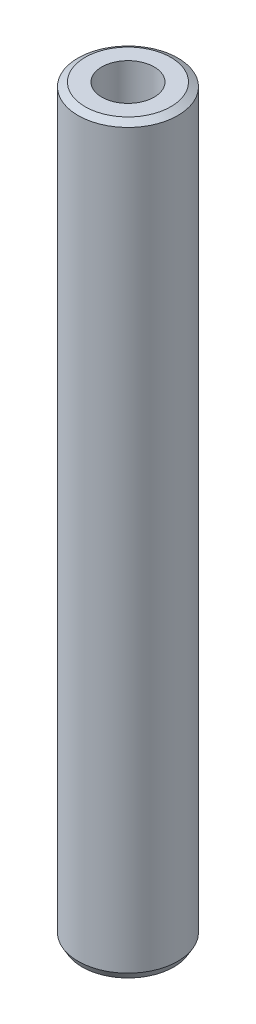
SolidWorks part; units mm, degrees
ref_plane "Front Plane" through (0, 0, 0) normal (0, 0, 1) x (1, 0, 0)
ref_plane "Top Plane" through (0, 0, 0) normal (0, 1, 0) x (1, 0, 0)
ref_plane "Right Plane" through (0, 0, 0) normal (1, 0, 0) x (0, 0, -1)
sketch "Sketch1" plane through (0, 0, 0) normal (0, 1, 0) x (1, 0, 0)
  circle A0 centre (0, 0) radius 20
  dimension "SHAFT_OD" = 40
extrude "Boss-Extrude1" add sketch "Sketch1" along normal blind 298.0615
sketch "Sketch2" plane through (0, 0, 0) normal (0, 1, 0) x (1, 0, 0)
  circle A0 centre (0, 0) radius 10.5065
  dimension "BORE_D" = 21.013
extrude "Cut-Extrude1" cut sketch "Sketch2" along normal through all
chamfer "Chamfer1" distance 1.6357 angle 60 2 edges at (0, 298.0615, 20) (0, 0, 20) first distance on face at (0, 298.0615, 20) first distance on face at (0, 0, 10.5065)
